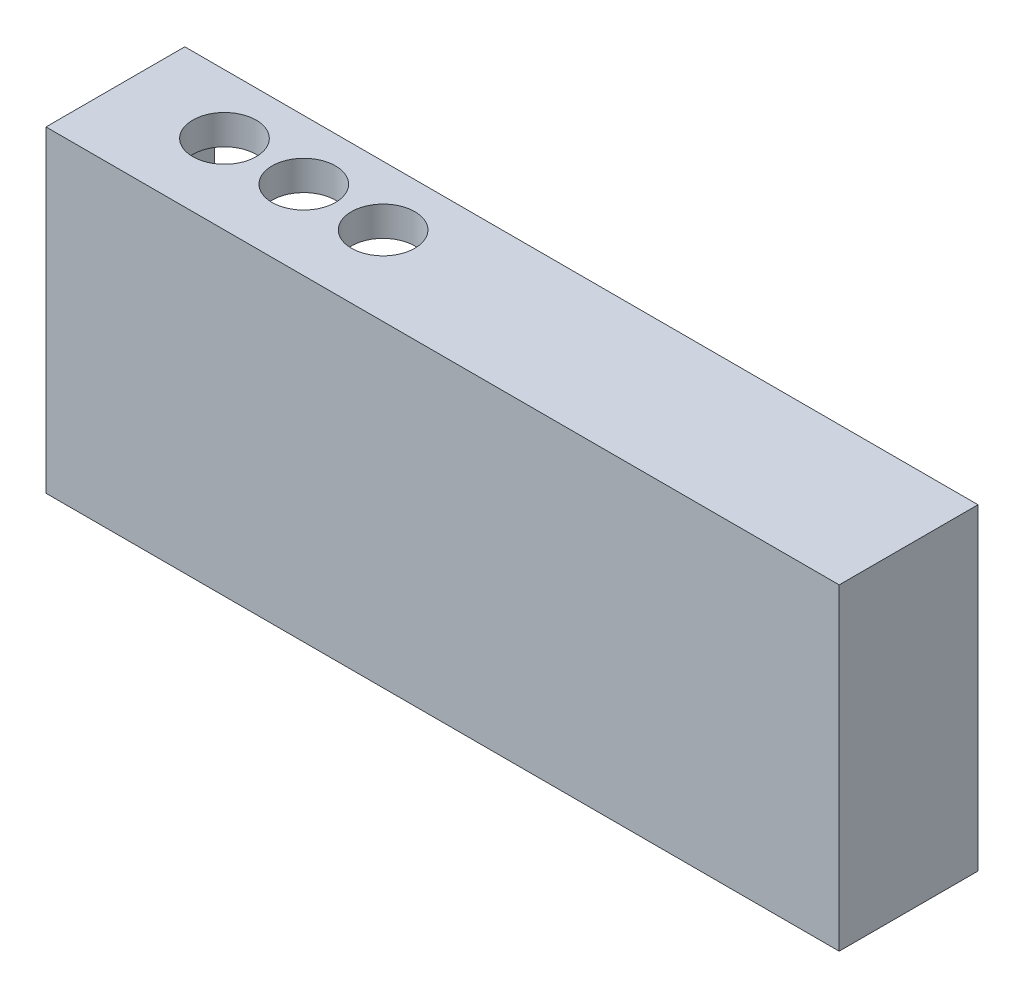
SolidWorks part; units mm, degrees
ref_plane "Alzado" through (0, 0, 0) normal (0, 0, 1) x (1, 0, 0)
ref_plane "Planta" through (0, 0, 0) normal (0, 1, 0) x (1, 0, 0)
ref_plane "Vista lateral" through (0, 0, 0) normal (1, 0, 0) x (0, 0, -1)
sketch "Croquis1" plane through (0, 0, 0) normal (0, 0, 1) x (1, 0, 0)
  line L1 (-100, -40) -> (100, -40)
  line L2 (-100, -40) -> (-100, 40)
  line L3 (-100, 40) -> (100, 40)
  line L4 (100, -40) -> (100, 40)
  line L5 (-100, -40) -> (100, 40) construction
  line L6 (-100, 40) -> (100, -40) construction
  point P0 (0, 0)
  dimension "D1" = 200
  dimension "D2" = 80
extrude "Saliente-Extruir1" add sketch "Croquis1" along normal blind 35
sketch "Croquis2" plane through (0, 0, 0) normal (0, 0, -1) x (-1, 0, 0)
  line L1 (-92.5, -32.5) -> (92.5, -32.5)
  line L2 (-92.5, -32.5) -> (-92.5, 32.5)
  line L3 (-92.5, 32.5) -> (92.5, 32.5)
  line L4 (92.5, -32.5) -> (92.5, 32.5)
  line L5 (-92.5, -32.5) -> (92.5, 32.5) construction
  line L6 (-92.5, 32.5) -> (92.5, -32.5) construction
  point P1 (0, 0)
  dimension "D1" = 185
  dimension "D2" = 65
extrude "Cortar-Extruir1" cut sketch "Croquis2" against normal blind 27.5
sketch "Croquis3" plane through (0, 40, 0) normal (0, 1, 0) x (1, 0, 0)
  line L0 (-35, -15) -> (-75, -15) construction
  line L6 (100, 0) -> (-100, 0) construction
  circle A0 centre (-75, -15) radius 8
  circle A1 centre (-55, -15) radius 8
  circle A2 centre (-35, -15) radius 8
  dimension "D1" = 16
  dimension "D2" = 16
  dimension "D3" = 16
  dimension "D4" = 15
  dimension "D5" = 20
  dimension "D6" = 20
extrude "Cortar-Extruir2" cut sketch "Croquis3" against normal blind 7.5
sketch "Croquis4" plane through (0, -40, 0) normal (0, -1, 0) x (1, 0, 0)
  line L0 (100, 17.5) -> (-100, 17.5) construction
  line L1 (100, 35) -> (100, 0) construction
  line L2 (-100, 35) -> (-100, 0) construction
  circle A0 centre (75, 17.5) radius 5.4
  dimension "D1" = 10.8
  dimension "D2" = 25
extrude "Cortar-Extruir3" cut sketch "Croquis4" against normal blind 7.5
sketch "Croquis5" plane through (0, 0, 0) normal (0, 0, -1) x (-1, 0, 0)
  line L0 (100, 40) -> (100, -40) construction
  line L1 (100, -40) -> (-100, -40) construction
  circle A0 centre (96.25, -36.25) radius 2.5092
  circle A1 centre (-96.25, -36.25) radius 2.5092
  circle A2 centre (-96.25, 36.25) radius 2.5092
  circle A3 centre (96.25, 36.25) radius 2.5092
  dimension "D1" = 5.0184
  dimension "D2" = 3.75
  dimension "D3" = 3.75
  dimension "D4" = 2
  dimension "D5" = 2
extrude "Cortar-Extruir4" cut sketch "Croquis5" against normal blind 2 contours A0 | A3 | A2 | A1 region at (-96.25, -36.25, 0) region at (96.25, -36.25, 0) region at (96.25, 36.25, 0) region at (-96.25, 36.25, 0)
